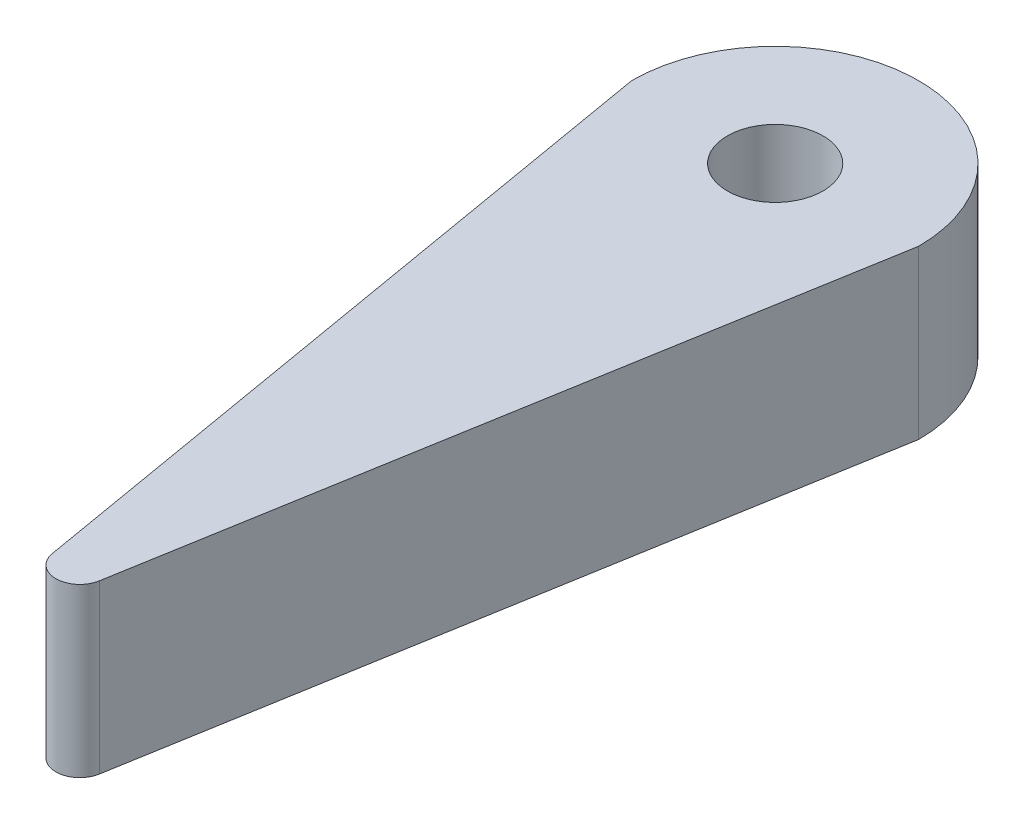
SolidWorks part; units mm, degrees
ref_plane "Front Plane" through (0, 0, 0) normal (0, 0, 1) x (1, 0, 0)
ref_plane "Top Plane" through (0, 0, 0) normal (0, 1, 0) x (1, 0, 0)
ref_plane "Right Plane" through (0, 0, 0) normal (1, 0, 0) x (0, 0, -1)
sketch "Sketch2" plane through (0, 0, 0) normal (0, 1, 0) x (1, 0, 0)
  line L0 (0, 0) -> (0, -70) construction
  line L1 (-12, 0) -> (0, -70)
  line L2 (0, -70) -> (12, 0)
  arc A0 (-12, 0) -> (12, 0) centre (0, 0) cw
  circle A1 centre (0, 0) radius 4
  dimension "D1" = 12
  dimension "D3" = 8
  dimension "D2" = 70
extrude "Boss-Extrude1" add sketch "Sketch2" along normal blind 14
fillet "Fillet1" radius 2 1 edges at (0, 7, 70)
